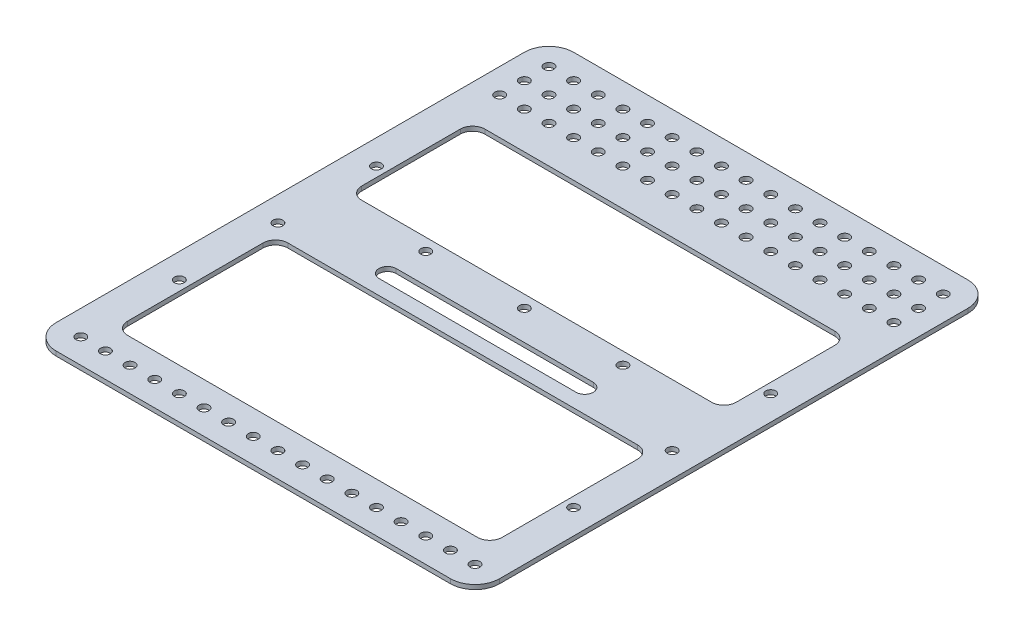
SolidWorks part; units mm, degrees
ref_plane "Front Plane" through (0, 0, 0) normal (0, 0, 1) x (1, 0, 0)
ref_plane "Top Plane" through (0, 0, 0) normal (0, 1, 0) x (1, 0, 0)
ref_plane "Right Plane" through (0, 0, 0) normal (1, 0, 0) x (0, 0, -1)
sketch "Sketch3" plane through (0, 0, 0) normal (0, 1, 0) x (1, 0, 0)
  line B0 (0, 0) -> (228.6, 0)
  line B1 (0, 0) -> (0, 266.7)
  line B2 (0, 266.7) -> (228.6, 266.7)
  line B3 (228.6, 0) -> (228.6, 266.7)
  line B4 (24.13, 101.6) -> (204.47, 101.6) construction
  line B5 (24.13, 101.6) -> (24.13, 25.4) construction
  line B6 (204.47, 101.6) -> (204.47, 25.4) construction
  line B7 (17.78, 107.95) -> (17.78, 25.4)
  line B8 (17.78, 107.95) -> (210.82, 107.95)
  line B9 (210.82, 107.95) -> (210.82, 25.4)
  line B10 (17.78, 127) -> (210.82, 127)
  line B11 (17.78, 127) -> (17.78, 209.55)
  line B12 (17.78, 209.55) -> (210.82, 209.55)
  line B13 (210.82, 127) -> (210.82, 209.55)
  circle B14 centre (12.7, 254) radius 2.54
  circle B15 centre (25.4, 254) radius 2.54
  circle B16 centre (38.1, 254) radius 2.54
  circle B17 centre (50.8, 254) radius 2.54
  circle B18 centre (63.5, 254) radius 2.54
  circle B19 centre (76.2, 254) radius 2.54
  circle B20 centre (88.9, 254) radius 2.54
  circle B21 centre (101.6, 254) radius 2.54
  circle B22 centre (114.3, 254) radius 2.54
  circle B23 centre (127, 254) radius 2.54
  circle B24 centre (139.7, 254) radius 2.54
  circle B25 centre (152.4, 254) radius 2.54
  circle B26 centre (165.1, 254) radius 2.54
  circle B27 centre (177.8, 254) radius 2.54
  circle B28 centre (190.5, 254) radius 2.54
  circle B29 centre (203.2, 254) radius 2.54
  circle B30 centre (215.9, 254) radius 2.54
  circle B31 centre (25.4, 241.3) radius 2.54
  circle B32 centre (38.1, 241.3) radius 2.54
  circle B33 centre (50.8, 241.3) radius 2.54
  circle B34 centre (63.5, 241.3) radius 2.54
  circle B35 centre (76.2, 241.3) radius 2.54
  circle B36 centre (88.9, 241.3) radius 2.54
  circle B37 centre (101.6, 241.3) radius 2.54
  circle B38 centre (114.3, 241.3) radius 2.54
  circle B39 centre (127, 241.3) radius 2.54
  circle B40 centre (139.7, 241.3) radius 2.54
  circle B41 centre (152.4, 241.3) radius 2.54
  circle B42 centre (165.1, 241.3) radius 2.54
  circle B43 centre (177.8, 241.3) radius 2.54
  circle B44 centre (190.5, 241.3) radius 2.54
  circle B45 centre (203.2, 241.3) radius 2.54
  circle B46 centre (215.9, 241.3) radius 2.54
  circle B47 centre (25.4, 228.6) radius 2.54
  circle B48 centre (38.1, 228.6) radius 2.54
  circle B49 centre (50.8, 228.6) radius 2.54
  circle B50 centre (63.5, 228.6) radius 2.54
  circle B51 centre (76.2, 228.6) radius 2.54
  circle B52 centre (88.9, 228.6) radius 2.54
  circle B53 centre (101.6, 228.6) radius 2.54
  circle B54 centre (114.3, 228.6) radius 2.54
  circle B55 centre (127, 228.6) radius 2.54
  circle B56 centre (139.7, 228.6) radius 2.54
  circle B57 centre (152.4, 228.6) radius 2.54
  circle B58 centre (165.1, 228.6) radius 2.54
  circle B59 centre (177.8, 228.6) radius 2.54
  circle B60 centre (190.5, 228.6) radius 2.54
  circle B61 centre (203.2, 228.6) radius 2.54
  circle B62 centre (215.9, 228.6) radius 2.54
  circle B63 centre (12.7, 241.3) radius 2.54
  circle B64 centre (12.7, 228.6) radius 2.54
  circle B65 centre (12.7, 12.7) radius 2.54
  circle B66 centre (25.4, 12.7) radius 2.54
  circle B67 centre (38.1, 12.7) radius 2.54
  circle B68 centre (50.8, 12.7) radius 2.54
  circle B69 centre (63.5, 12.7) radius 2.54
  circle B70 centre (76.2, 12.7) radius 2.54
  circle B71 centre (88.9, 12.7) radius 2.54
  circle B72 centre (101.6, 12.7) radius 2.54
  circle B73 centre (114.3, 12.7) radius 2.54
  circle B74 centre (127, 12.7) radius 2.54
  circle B75 centre (139.7, 12.7) radius 2.54
  circle B76 centre (152.4, 12.7) radius 2.54
  circle B77 centre (165.1, 12.7) radius 2.54
  circle B78 centre (177.8, 12.7) radius 2.54
  circle B79 centre (190.5, 12.7) radius 2.54
  circle B80 centre (203.2, 12.7) radius 2.54
  circle B81 centre (215.9, 12.7) radius 2.54
  circle B82 centre (12.7, 114.3) radius 2.54
  circle B83 centre (63.5, 114.3) radius 2.54
  circle B84 centre (114.3, 114.3) radius 2.54
  circle B85 centre (165.1, 114.3) radius 2.54
  circle B86 centre (215.9, 114.3) radius 2.54
  circle B87 centre (12.7, 165.1) radius 2.54
  circle B88 centre (215.9, 165.1) radius 2.54
  circle B89 centre (12.7, 63.5) radius 2.54
  circle B90 centre (215.9, 63.5) radius 2.54
  line B91 (17.78, 25.4) -> (210.82, 25.4)
sketch_block_instance "Block-Battery Holder-1"
sketch_block "Block-Battery Holder" parameters "D5"=5.08, "D10"=5.08, "D13"=5.08, "D1"=228.6, "D2"=19.05, "D3"=12.7, "D4"=12.7, "D6"=12.7, "D7"=12.7, "D8"=12.7, "D9"=12.7, "D11"=12.7, "D12"=12.7, "D14"=50.8, "D15"=50.8, "D16"=50.8, "D17"=76.2
extrude "Boss-Extrude3" add sketch "Sketch3" along normal blind 2.286
sketch "Sketch6" plane through (0, 2.286, 0) normal (0, 1, 0) x (1, 0, 0)
  line L0 (17.78, 209.55) -> (17.78, 127) construction
  line L1 (210.82, 127) -> (17.78, 127)
  line L2 (210.82, 127) -> (210.82, 146.05)
  line L3 (210.82, 146.05) -> (17.78, 146.05)
  line L4 (17.78, 127) -> (17.78, 146.05)
  dimension "D1" = 19.05
extrude "Boss-Extrude4" add sketch "Sketch6" against normal up to surface (2.286 mm away) up to face at (12.7, 0, -60.96)
sketch "Sketch8" plane through (0, 2.286, 0) normal (0, 1, 0) x (1, 0, 0)
  circle A0 centre (63.5, 114.3) radius 2.54 construction
  circle A1 centre (114.3, 114.3) radius 2.54 construction
  circle A2 centre (165.1, 114.3) radius 2.54 construction
  circle A3 centre (63.5, 114.3) radius 2.54
  circle A4 centre (114.3, 114.3) radius 2.54
  circle A5 centre (165.1, 114.3) radius 2.54
extrude "Boss-Extrude5" add sketch "Sketch8" against normal through all
sketch "Sketch9" plane through (0, 2.286, 0) normal (0, 1, 0) x (1, 0, 0)
  line L1 (210.82, 107.95) -> (17.78, 107.95) construction
  line L2 (165.1, 120.015) -> (63.5, 120.015) construction
  line L3 (165.1, 115.57) -> (63.5, 115.57)
  line L4 (165.1, 124.46) -> (63.5, 124.46)
  line L6 (210.82, 146.05) -> (210.82, 209.55) construction
  line L7 (210.82, 146.05) -> (17.78, 146.05) construction
  circle A0 centre (165.1, 139.7) radius 2.54
  circle A1 centre (114.3, 139.7) radius 2.54
  arc A4 (165.1, 115.57) -> (165.1, 124.46) centre (165.1, 120.015) ccw
  circle A5 centre (63.5, 139.7) radius 2.54
  arc A6 (63.5, 124.46) -> (63.5, 115.57) centre (63.5, 120.015) ccw
  point P4 (69.0165, 122.0242)
  point P6 (114.3, 120.015)
  point P11 (0, 0)
  point P17 (31.1013, 92.4734)
  point P18 (31.1013, 92.4734)
  point P19 (31.1013, 92.4734)
  point P22 (0, 0)
  point P23 (63.5, 137.5664)
  dimension "D1" = 5.08
  dimension "D2" = 7.62
  dimension "D3" = 45.72
  dimension "D4" = 50.8
  dimension "D5" = 50.8
  dimension "D6" = 5.08
  dimension "D7" = 6.35
  dimension "D8" = 8.89
extrude "Cut-Extrude2" cut sketch "Sketch9" against normal through all
fillet "Fillet5" radius 12.7 4 edges at (0, 1.143, -266.7) (228.6, 1.143, -266.7) (228.6, 1.143, 0) (0, 1.143, 0)
fillet "Fillet6" radius 6.35 8 edges at (210.82, 1.143, -209.55) (17.78, 1.143, -209.55) (17.78, 1.143, -107.95) (17.78, 1.143, -25.4) (210.82, 1.143, -25.4) (210.82, 1.143, -107.95) (17.78, 1.143, -146.05) (210.82, 1.143, -146.05)
sketch "Sketch4" plane through (0, 0, 0) normal (0, -1, 0) x (1, 0, 0)
  line L0 (-1000, 0) -> (49000, 0) construction
  line L1 (0, -1000) -> (0, 49000) construction
  point P4 (0, 0)
sketch "Sketch5" plane through (0, 0, 0) normal (0, -1, 0) x (1, 0, 0)
  line L0 (204.47, -209.55) -> (24.13, -209.55) construction
  line L1 (17.78, -203.2) -> (17.78, -152.4) construction
  line L2 (55.88, -171.45) -> (170.18, -171.45) construction
  line L3 (55.88, -171.45) -> (55.88, -57.15) construction
  circle A0 centre (55.88, -171.45) radius 2.54
  circle A1 centre (170.18, -171.45) radius 2.54
  circle A2 centre (170.18, -57.15) radius 2.54
  circle A3 centre (55.88, -57.15) radius 2.54
  dimension "D1" = 38.1
  dimension "D2" = 38.1
  dimension "D3" = 5.08
  dimension "D6" = 114.3
  dimension "D7" = 114.3
  dimension "D4" = 2
  dimension "D5" = 2
